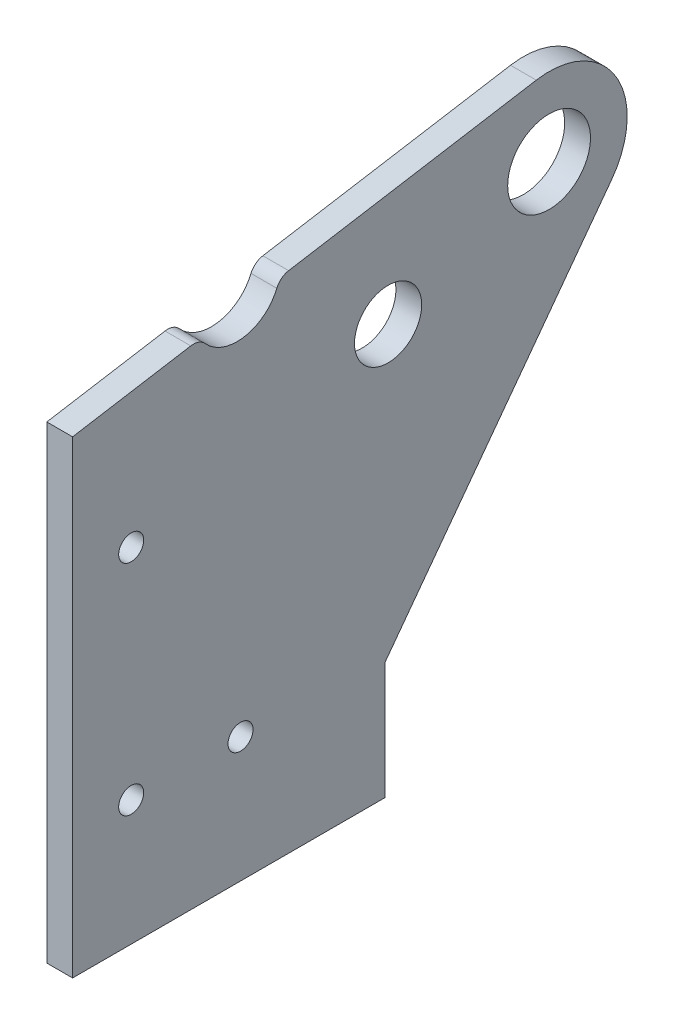
SolidWorks part; units mm, degrees
ref_plane "Front" through (0, 0, 0) normal (0, 0, 1) x (1, 0, 0)
ref_plane "Top" through (0, 0, 0) normal (0, 1, 0) x (1, 0, 0)
ref_plane "Right" through (0, 0, 0) normal (1, 0, 0) x (0, 0, -1)
sketch "Sketch1" plane through (-39, 0, 0) normal (-1, 0, 0) x (0, 0, 1)
  line L2 (61, 0) -> (21, 0)
  line L3 (61, 60) -> (61, 0)
  line L6 (-8.0246, 54.033) -> (21, 15)
  line L7 (61, 60) -> (1.6393, 69.8647)
  line L8 (21, 15) -> (21, 0)
  line L9 (-65, 60) -> (65, 60) construction
  line L10 (61, 0) -> (31, 0) construction
  line L11 (65, -6) -> (65, 60) construction
  circle A11 centre (20.6096, 52.3031) radius 4.3
  circle A12 centre (20.6096, 52.3031) radius 4.3
  arc A13 (-8.0246, 54.033) -> (1.6393, 69.8647) centre (0, 60) cw
  circle A14 centre (0, 60) radius 5.3
  circle A15 centre (0, 60) radius 5.3
  dimension "D5" = 10
  dimension "D3" = 40
  dimension "D4" = 15
  dimension "D6" = 4
  dimension "D1" = 0.3
  dimension "D2" = 0.3
extrude "Boss-Extrude1" add sketch "Sketch1" along normal offset from surface (3.3 mm away) 0.3 offset beyond the face yes
sketch "Sketch2" plane through (-42.3, 0, 0) normal (-1, 0, 0) x (0, 0, 1)
  circle A3 centre (39.9311, 65.5231) radius 5.5
  circle A4 centre (39.9311, 65.5231) radius 5.5
  dimension "D1" = 4
extrude "Cut-Extrude1" cut sketch "Sketch2" against normal through all contours A4
fillet "Fillet1" radius 2 2 edges at (-40.65, 62.7154, 44.6604) (-40.65, 64.3959, 34.5479)
sketch "Sketch3" plane through (-39, 0, 0) normal (1, 0, 0) x (0, 0, -1)
  circle A0 centre (-53.5, 44) radius 1.6 construction
  circle A1 centre (-39.5, 16) radius 1.6 construction
  circle A2 centre (-53.5, 16) radius 1.6 construction
  circle A3 centre (-53.5, 44) radius 1.6
  circle A4 centre (-39.5, 16) radius 1.6
  circle A5 centre (-53.5, 16) radius 1.6
extrude "Cut-Extrude2" cut sketch "Sketch3" against normal through all
